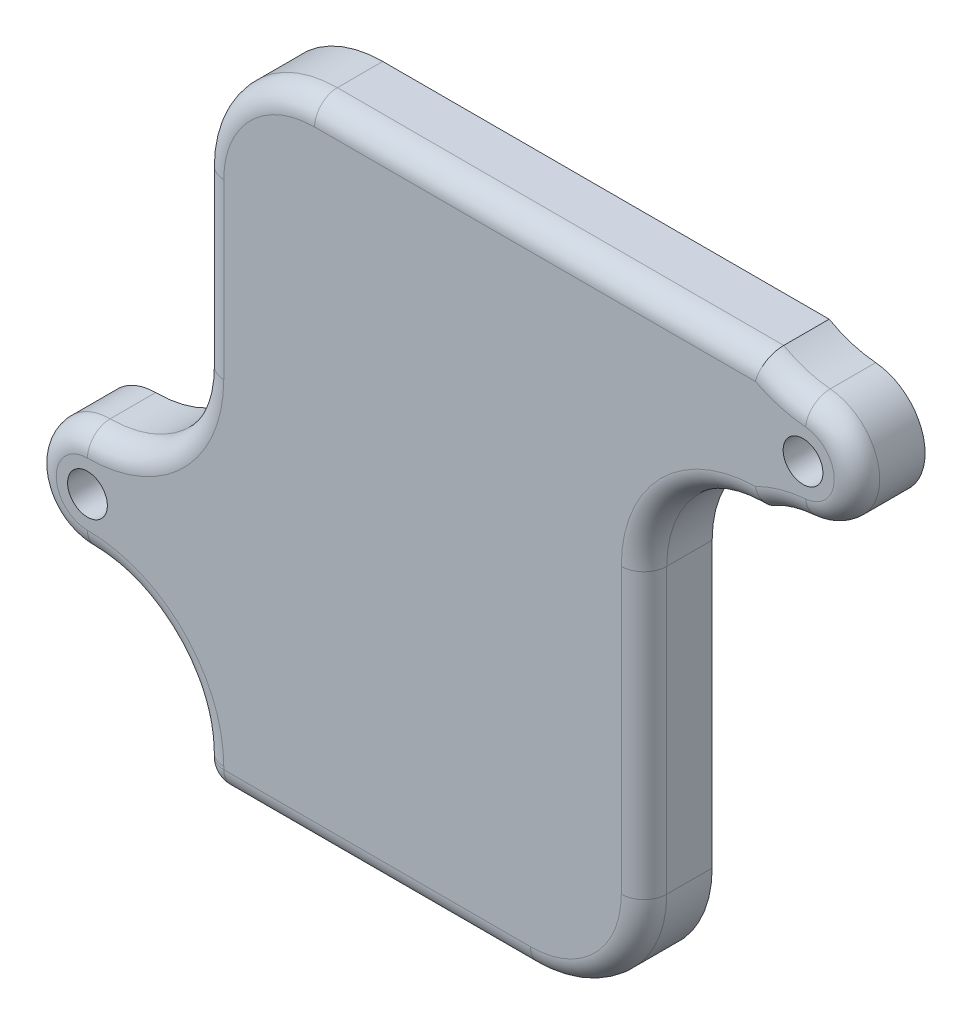
SolidWorks part; units mm, degrees
ref_plane "Front Plane" through (0, 0, 0) normal (0, 0, 1) x (1, 0, 0)
ref_plane "Top Plane" through (0, 0, 0) normal (0, 1, 0) x (1, 0, 0)
ref_plane "Right Plane" through (0, 0, 0) normal (1, 0, 0) x (0, 0, -1)
sketch "Sketch1" plane through (0, 0, 0) normal (0, 0, 1) x (1, 0, 0)
  line L1 (19.5, 28.5) -> (-19.5, 28.5)
  line L2 (19.5, 28.5) -> (19.5, -28.5)
  line L3 (19.5, -28.5) -> (-19.5, -28.5)
  line L4 (-19.5, 28.5) -> (-19.5, -28.5)
  line L5 (19.5, 28.5) -> (-19.5, -28.5) construction
  line L6 (19.5, -28.5) -> (-19.5, 28.5) construction
  point P0 (0, 0)
  dimension "D1" = 39
  dimension "D2" = 57
extrude "Boss-Extrude1" add sketch "Sketch1" along normal blind 6
sketch "Sketch2" plane through (0, 0, 6) normal (0, 0, 1) x (1, 0, 0)
  line L0 (19.5, -28.5) -> (19.5, 28.5) construction
  line L1 (-19.5, 28.5) -> (-19.5, -28.5) construction
  line L2 (19.5, 28.5) -> (-19.5, 28.5) construction
  line L3 (33.5, 27.25) -> (19.5, 27.25)
  line L4 (33.5, 17.75) -> (19.5, 17.75)
  line L5 (19.5, 17.75) -> (19.5, 27.25)
  line L6 (-29.5, -6.75) -> (-19.5, -6.75)
  line L7 (-19.5, -6.75) -> (-19.5, -16.25)
  line L8 (-19.5, -16.25) -> (-29.5, -16.25)
  circle A0 centre (-29.5, -11.5) radius 4.75
  circle A1 centre (-29.5, -11.5) radius 1.75
  circle A2 centre (33.5, 22.5) radius 4.75
  circle A3 centre (33.5, 22.5) radius 1.75
  line M1 (-19.5, 28.5) -> (-19.5, -28.5)
  line M3 (19.5, -28.5) -> (19.5, 28.5)
  dimension "D1" = 3.5
  dimension "D2" = 3.5
  dimension "D3" = 3
  dimension "D4" = 3
  dimension "D5" = 14
  dimension "D6" = 10
  dimension "D7" = 6
  dimension "D8" = 40
extrude "Boss-Extrude2" add sketch "Sketch2" against normal up to surface (6 mm away) contours A2 L3 L4 M3 | A0 L8 L6 M1 | A0 A1 | A2 A3 region at (24.6894, 22.5, 6) region at (36.7638, 25.7638, 6) region at (-22.7243, -11.5, 6) region at (-26.2362, -8.2362, 6) up to face at (0, 0, 0)
sketch "Sketch3" plane through (0, 0, 6) normal (0, 0, 1) x (1, 0, 0)
  line L0 (19.5, -28.5) -> (19.5, 17.75) construction
  line L1 (19.5, -8.5) -> (4.5, -8.5)
  line L2 (19.5, -8.5) -> (19.5, -28.5)
  line L3 (19.5, -28.5) -> (4.5, -28.5)
  line L4 (4.5, -8.5) -> (4.5, -28.5)
  line L5 (-19.5, -28.5) -> (19.5, -28.5) construction
  dimension "D1" = 15
  dimension "D2" = 20
extrude "Cut-Extrude1" [suppressed] cut sketch "Sketch3" against normal blind 3
fillet "Fillet2" [suppressed] radius 4
fillet "Fillet4" radius 10 2 edges at (-19.5, 28.5, 3) (19.5, -28.5, 3)
sketch "Sketch4" plane through (0, 0, 6) normal (0, 0, 1) x (1, 0, 0)
  line L0 (33.5, 27.25) -> (19.5, 27.25) construction
  line L1 (19.5, 28.5) -> (29.8047, 28.5)
  line L2 (19.5, 28.5) -> (19.5, 16.5)
  line L3 (19.5, 16.5) -> (29.8047, 16.5)
  line L4 (29.8047, 28.5) -> (29.8047, 16.5)
  dimension "D1" = 12
  dimension "D2" = 1.25
extrude "Boss-Extrude3" add sketch "Sketch4" against normal up to surface (6 mm away) contours L2 L1 L4 L3 up to face at (0.5714, 3.1429, 0)
fillet "Fillet5" radius 10 5 edges at (29.8047, 17.75, 3) (29.8047, 27.25, 3) (19.5, 16.5, 3) (-19.5, -6.75, 3) (-19.5, -16.25, 3)
sketch "Sketch5" plane through (0, 0, 0) normal (0, 0, -1) x (-1, 0, 0)
  line L0 (-29.0521, 19.4923) -> (-29.0521, 19.4923)
  line L1 (-16.5, 6.5) -> (-16.5, -18.5)
  line L2 (-9.5, -25.5) -> (16.5217, -25.5)
  line L3 (16.5217, -25.5) -> (16.5217, -25.5)
  line L4 (16.5, 3.25) -> (16.5, 18.5)
  line L5 (9.5, 25.5) -> (-20.1506, 25.5)
  line L6 (-29.8047, 16.5) -> (-29.5, 16.5)
  line L7 (-19.5, 6.5) -> (-19.5, -18.5)
  line L8 (-9.5, -28.5) -> (19.5, -28.5)
  line L9 (19.5, -28.5) -> (19.5, -26.25)
  line L10 (19.5, 3.25) -> (19.5, 18.5)
  line L11 (9.5, 28.5) -> (-29.8047, 28.5)
  line L12 (-29.8047, 16.5) -> (-29.5, 16.5)
  line L13 (-19.5, 6.5) -> (-19.5, -18.5)
  line L14 (-9.5, -28.5) -> (19.5, -28.5)
  line L15 (19.5, -28.5) -> (19.5, -26.25)
  line L16 (19.5, 3.25) -> (19.5, 18.5)
  line L17 (9.5, 28.5) -> (-20.2983, 28.5)
  line L18 (-20.1506, 15.5327) -> (-20.1506, 25.5)
  line L19 (9.5, 25.5) -> (-29.068, 25.5) construction
  line L21 (20.3076, -5.9424) -> (20.5767, -16.7962)
  line L23 (9.5, 28.5) -> (-29.8047, 28.5) construction
  arc A0 (-16.5, 6.5) -> (-20.1506, 15.5327) centre (-29.5, 6.5) ccw
  arc A1 (-16.5, -18.5) -> (-9.5, -25.5) centre (-9.5, -18.5) ccw
  arc A2 (20.5767, -16.7962) -> (16.5217, -25.5) centre (29.5, -26.25) ccw
  arc A4 (16.5, 3.25) -> (20.3076, -5.9424) centre (29.5, 3.25) ccw
  arc A5 (16.5, 18.5) -> (9.5, 25.5) centre (9.5, 18.5) ccw
  arc A7 (-33.647, 24.2438) -> (-33.647, 20.7562) centre (-33.5, 22.5) ccw
  arc A9 (-19.5, 6.5) -> (-29.5, 16.5) centre (-29.5, 6.5) ccw
  arc A10 (-19.5, -18.5) -> (-9.5, -28.5) centre (-9.5, -18.5) ccw
  arc A11 (29.5, -16.25) -> (19.5, -26.25) centre (29.5, -26.25) ccw
  arc A12 (29.5, -16.25) -> (29.5, -6.75) centre (29.5, -11.5) ccw
  arc A13 (19.5, 3.25) -> (29.5, -6.75) centre (29.5, 3.25) ccw
  arc A14 (19.5, 18.5) -> (9.5, 28.5) centre (9.5, 18.5) ccw
  arc A15 (-33.899, 27.2332) -> (-29.8047, 28.5) centre (-34.739, 37.1979) ccw
  arc A16 (-33.899, 27.2332) -> (-33.899, 17.7668) centre (-33.5, 22.5) ccw
  arc A17 (-29.8047, 16.5) -> (-33.899, 17.7668) centre (-34.739, 7.8021) ccw
  arc A18 (-19.5, 6.5) -> (-29.5, 16.5) centre (-29.5, 6.5) ccw
  arc A19 (-19.5, -18.5) -> (-9.5, -28.5) centre (-9.5, -18.5) ccw
  arc A20 (29.5, -16.25) -> (19.5, -26.25) centre (29.5, -26.25) ccw
  arc A21 (29.5, -16.25) -> (29.5, -6.75) centre (29.5, -11.5) ccw
  arc A22 (19.5, 3.25) -> (29.5, -6.75) centre (29.5, 3.25) ccw
  arc A23 (19.5, 18.5) -> (9.5, 28.5) centre (9.5, 18.5) ccw
  arc A24 (-33.899, 27.2332) -> (-29.8047, 28.5) centre (-34.739, 37.1979) ccw
  arc A25 (-33.899, 27.2332) -> (-33.899, 17.7668) centre (-33.5, 22.5) ccw
  arc A26 (-29.8047, 16.5) -> (-33.899, 17.7668) centre (-34.739, 7.8021) ccw
  arc A27 (-16.5, 6.5) -> (-29.0521, 19.4923) centre (-29.5, 6.5) ccw construction
  arc A28 (-29.0521, 19.4923) -> (-33.647, 20.7562) centre (-34.739, 7.8021) ccw construction
  arc A29 (-33.647, 24.2438) -> (-29.068, 25.5) centre (-34.739, 37.1979) ccw construction
  arc A30 (16.5, 3.25) -> (29.5, -9.75) centre (29.5, 3.25) ccw construction
  arc A31 (29.5, -13.25) -> (16.5217, -25.5) centre (29.5, -26.25) ccw construction
  arc A32 (29.5, -13.25) -> (29.5, -9.75) centre (29.5, -11.5) ccw construction
  dimension "D1" = 0
  dimension "D2" = 3
extrude "Cut-Extrude2" cut sketch "Sketch5" against normal blind 3.5 contours L4 A5 L5 L18 A0 L1 A1 L2 A2 L21 A4 region at (-0.1945, 0.0716, 0)
fillet "Fillet7" radius 2 1 edges at (-19.5, -28.5, 3)
fillet "Fillet8" radius 2 15 edges at (31.7832, 17.3553, 6) (31.7832, 27.6447, 6) (22.4289, 13.5711, 6) (19.5, -6, 6) (16.5711, -25.5711, 6) (-4, -28.5, 6) (-18.9142, -27.9142, 6) (-19.5, -26.375, 6) (-22.4289, -19.1789, 6) (-34.25, -11.5, 6) (-22.4289, -3.8211, 6) (-19.5, 10.875, 6) (-16.5711, 25.5711, 6) (38.25, 22.5, 6) (10.1524, 28.5, 6)
fillet "Fillet9" radius 2 11 edges at (-17.4896, -1.7249, 3.5) (-20.4422, -11.3693, 3.5) (-17.7161, -20.76, 3.5) (-3.5108, -25.5, 3.5) (14.4497, -23.4497, 3.5) (16.5, -6, 3.5) (17.4472, 11.3712, 3.5) (20.1506, 20.5163, 3.5) (5.3253, 25.5, 3.5) (-14.4497, 23.4497, 3.5) (-16.5, 10.875, 3.5)
